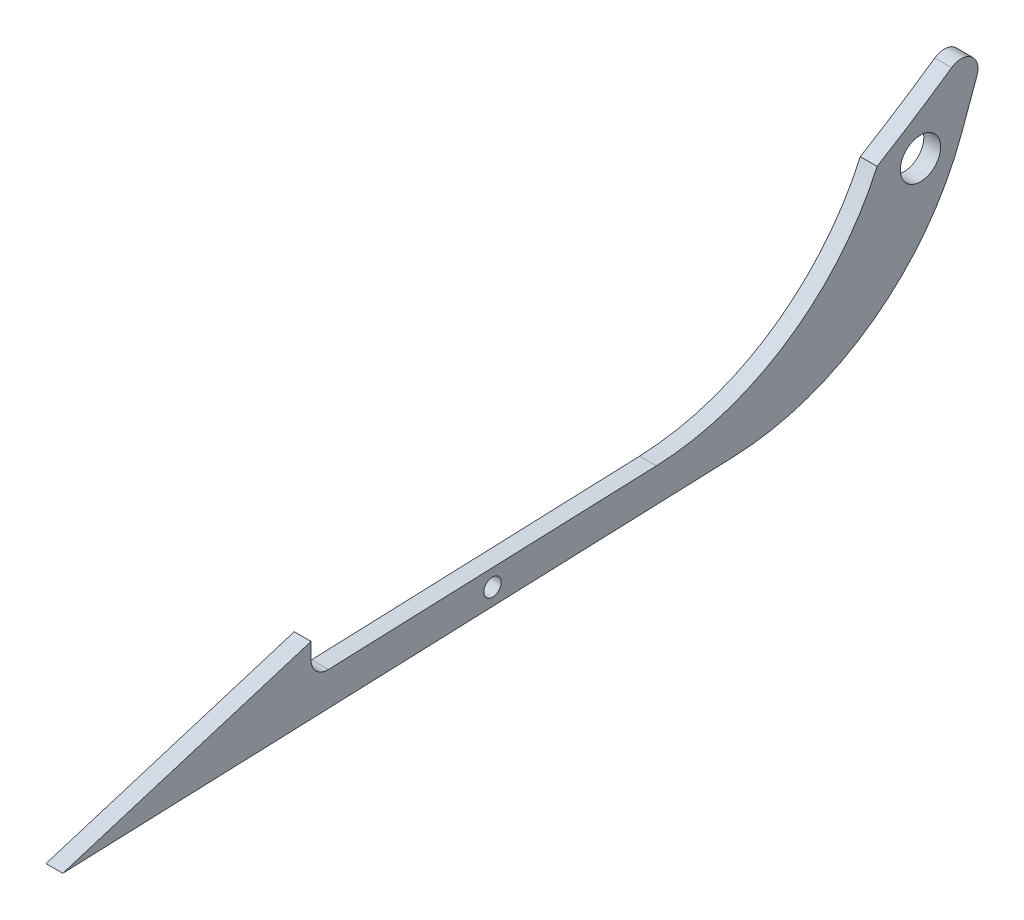
SolidWorks part; units mm, degrees
material "Ti-5Al-2.5Sn Отожженный (SS)"
ref_plane "Спереди" through (0, 0, 0) normal (0, 0, 1) x (1, 0, 0)
ref_plane "Сверху" through (0, 0, 0) normal (0, 1, 0) x (1, 0, 0)
ref_plane "Справа" through (0, 0, 0) normal (1, 0, 0) x (0, 0, -1)
sketch "Эскиз1" plane through (0, 0, 0) normal (1, 0, 0) x (0, 0, -1)
  line L0 (98.8217, -16.4384) -> (98.8217, -25.8841) construction
  line L1 (98.8217, -25.8841) -> (-151.1783, -25.8841) construction
  line L2 (126.2377, 58.8863) -> (98.8217, -16.4384)
  line L3 (-77.3456, -13.0873) -> (75.5394, -7.3109)
  line L4 (90.9757, 35.1) -> (75.5394, -7.3109)
  line L5 (-151.1783, -25.8841) -> (98.8217, -16.4384)
  line L6 (-151.1783, -25.8841) -> (-77.3456, -3.0802)
  line L7 (-77.3456, -3.0802) -> (-77.3456, -13.0873)
  circle A0 centre (103.8702, 30.6985) radius 6
  arc A1 (126.2377, 58.8863) -> (90.9757, 35.1) centre (-128.3125, 398.214) cw
  dimension "D1" = 250
  dimension "D2" = 15
extrude "Бобышка-Вытянуть1" add sketch "Эскиз1" along normal blind 5
fillet "Скругление1" radius 5 1 edges at (2.5, -13.0873, 77.3456)
fillet "Скругление2" radius 75 2 edges at (2.5, -16.4384, -98.8217) (2.5, -7.3109, -75.5394)
fillet "Скругление3" radius 5 1 edges at (2.5, 58.8863, -126.2377)
sketch "Эскиз3" plane through (5, 0, 0) normal (1, 0, 0) x (0, 0, -1)
  line L0 (-23.4027, -11.0492) -> (-23.4027, -21.0564) construction
  line L1 (25.3514, -9.2072) -> (-72.1568, -12.8913) construction
  line L2 (-151.1783, -25.8841) -> (48.4253, -18.3425) construction
  circle A0 centre (-23.4027, -16.0528) radius 2.6
extrude "Вырез-Вытянуть1" cut sketch "Эскиз3" against normal through all
